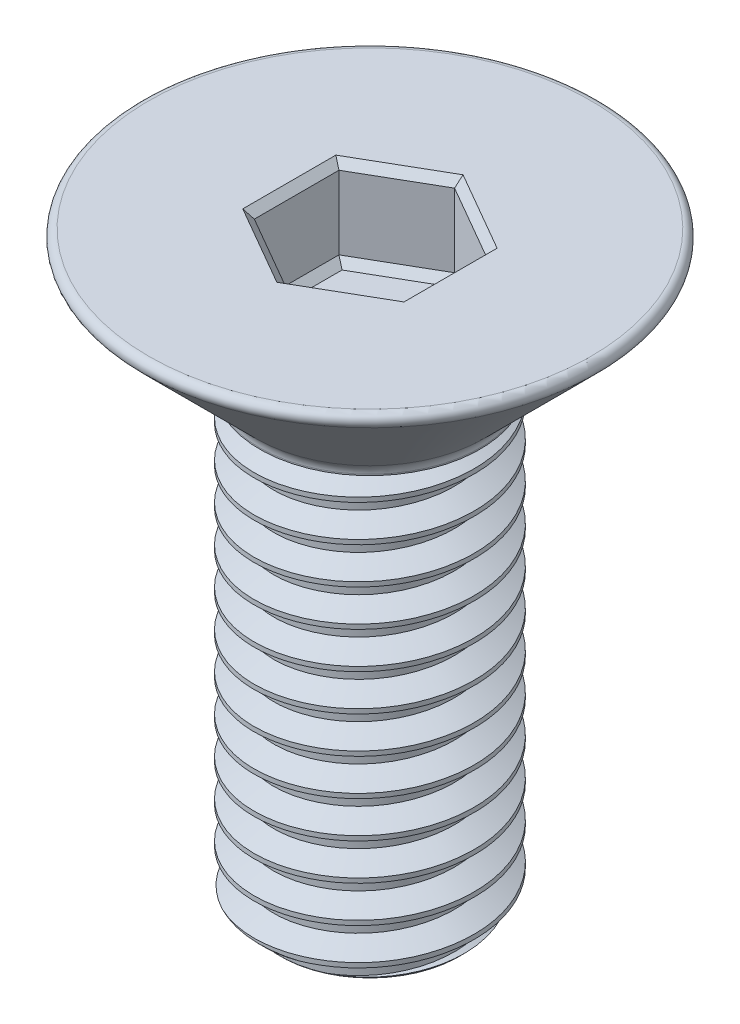
SolidWorks part; units mm, degrees
material "AISI Type A2 Tool Steel"
ref_plane "Front Plane" through (0, 0, 0) normal (0, 0, 1) x (1, 0, 0)
ref_plane "Top Plane" through (0, 0, 0) normal (0, 1, 0) x (1, 0, 0)
ref_plane "Right Plane" through (0, 0, 0) normal (1, 0, 0) x (0, 0, -1)
sketch "Sketch1" plane through (0, 0, 0) normal (0, 1, 0) x (1, 0, 0)
  circle A0 centre (0, 0) radius 1.5
  dimension "D1" = 3
extrude "Boss-Extrude1" add sketch "Sketch1" along normal blind 6.14
thread "Thread1" pitch 0.5 method cut profile "Thread Profile1" start angle 0, offset 1, length 0, pitch 0.5, diameter 3
ref_plane "Plane1" through (-1.5, 7.14, 0) normal (0, 0, 1) x (-1, 0, 0)
sketch "Thread Profile1" plane through (-1.5, 7.14, 0) normal (0, 0, 1) x (-1, 0, 0)
  line L0 (0, 0) -> (0, 0.5) construction
  line L11 (0, 0) -> (0, 0.4375)
  line L12 (0, 0.4375) -> (-0.2706, 0.2812)
  line L13 (-0.2706, 0.2812) -> (-0.2706, 0.1562)
  line L15 (-0.2706, 0.1562) -> (0, 0)
  line L17 (-0.2706, 0.2187) -> (0, 0.2187) construction
  point P2 (0, 0)
  dimension "Pitch" = 0.5
  dimension "Profile_Angle" = 60
  dimension "Profile_Land" = 0.125
  dimension "Profile_Height" = 0.2706
sketch "Sketch5" plane through (0, 6.14, 0) normal (0, 1, 0) x (1, 0, 0)
  circle A0 centre (0, 0) radius 1.5
  dimension "D1" = 3
extrude "Boss-Extrude2" add sketch "Sketch5" along normal blind 0.1
sketch "Sketch6" plane through (0, 6.24, 0) normal (0, 1, 0) x (1, 0, 0)
  circle A0 centre (0, 0) radius 1.5
  dimension "D1" = 3
extrude "Boss-Extrude3" add sketch "Sketch6" along normal blind 1.76 draft 45 draft outward yes
sketch "Sketch7" plane through (0, 0, 0) normal (0, 0, 1) x (1, 0, 0)
  line L0 (0, 0) -> (0, 0.1997) construction
  line L1 (0, 0) -> (1.51, 0) construction
  line L2 (1.51, 0) -> (1.51, 0.3)
  line L3 (1.51, 0.3) -> (1.21, 0)
  line L4 (1.21, 0) -> (1.51, 0)
  dimension "D1" = 45
  dimension "D2" = 0.3
  dimension "D3" = 1.51
revolve "Cut-Revolve1" cut sketch "Sketch7" angle 360 about L0
fillet "Fillet1" radius 0.1 1 edges at (0, 8, 3.26)
fillet "Fillet2" radius 0.2 1 edges at (0, 6.24, 1.5)
sketch "Sketch8" plane through (0, 8, 0) normal (0, 1, 0) x (1, 0, 0)
  line L1 (0, 1.1547) -> (-1, 0.5774)
  line L2 (-1, 0.5774) -> (-1, -0.5774)
  line L3 (-1, -0.5774) -> (0, -1.1547)
  line L4 (0, -1.1547) -> (1, -0.5774)
  line L5 (1, -0.5774) -> (1, 0.5774)
  line L6 (1, 0.5774) -> (0, 1.1547)
  circle A0 centre (0, 0) radius 1 construction
  dimension "D1" = 2
extrude "Cut-Extrude1" cut sketch "Sketch8" against normal blind 1.1
chamfer "Chamfer1" distance 0.1 angle 45 6 edges at (-1, 8, 0) (-0.5, 8, 0.866) (0.5, 8, 0.866) (1, 8, 0) (0.5, 8, -0.866) (-0.5, 8, -0.866)
sketch "Sketch9" plane through (0, 6.9, 0) normal (0, 1, 0) x (1, 0, 0)
  line L1 (0, 1.1547) -> (-1, 0.5774)
  line L2 (-1, 0.5774) -> (-1, -0.5774)
  line L3 (-1, -0.5774) -> (0, -1.1547)
  line L4 (0, -1.1547) -> (1, -0.5774)
  line L5 (1, -0.5774) -> (1, 0.5774)
  line L6 (1, 0.5774) -> (0, 1.1547)
  circle A0 centre (0, 0) radius 1 construction
extrude "Cut-Extrude2" cut sketch "Sketch9" against normal blind 0.1 draft 45
